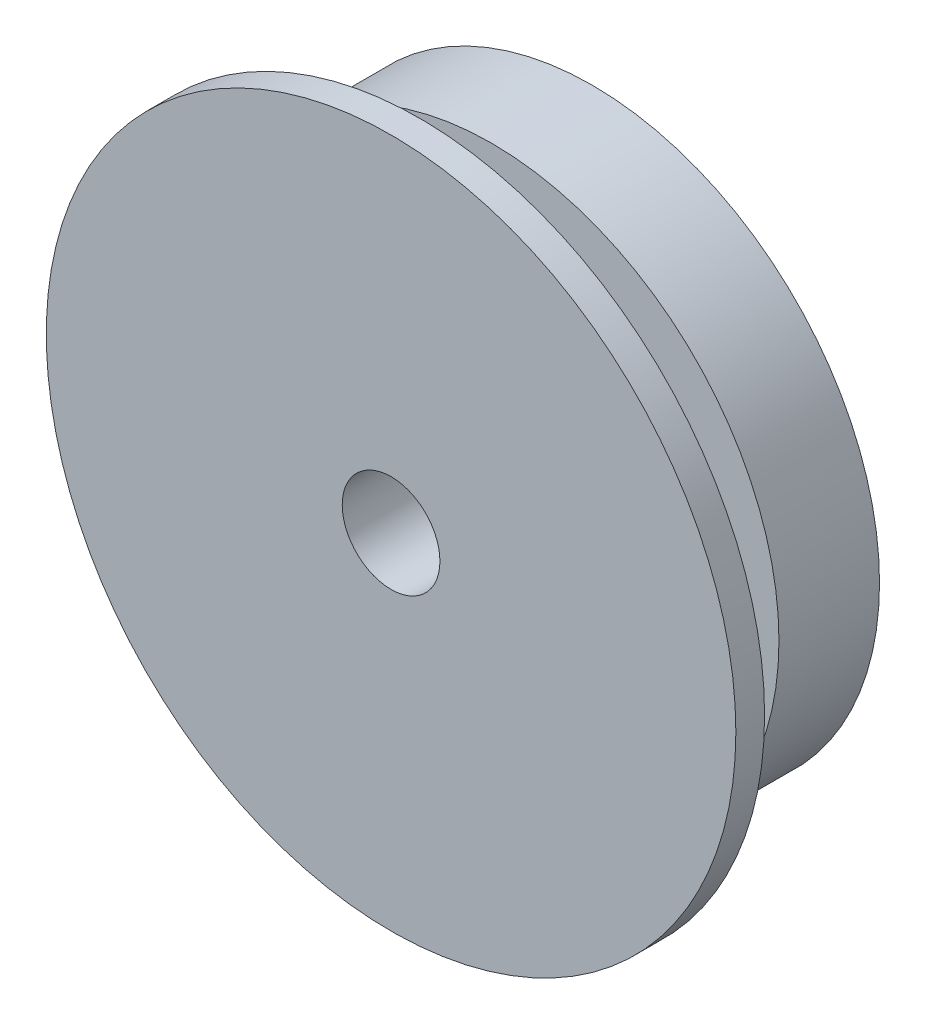
SolidWorks part; units mm, degrees
material "Resina de melamina"
ref_plane "Alzado" through (0, 0, 0) normal (0, 0, 1) x (1, 0, 0)
ref_plane "Planta" through (0, 0, 0) normal (0, 1, 0) x (1, 0, 0)
ref_plane "Vista lateral" through (0, 0, 0) normal (1, 0, 0) x (0, 0, -1)
sketch "Croquis1" plane through (0, 0, 0) normal (0, 0, 1) x (1, 0, 0)
  circle A0 centre (0, 0) radius 11
  circle A1 centre (0, 0) radius 25
  dimension "D1" = 50
  dimension "D2" = 22
extrude "Saliente-Extruir1" add sketch "Croquis1" along normal blind 19
ref_plane "Plano1" through (0, 0, 6) normal (0, 0, -1) x (-1, 0, 0)
sketch "Croquis3" plane through (0, 0, 6) normal (0, 0, -1) x (-1, 0, 0)
  circle A0 centre (0, 0) radius 11
  circle A1 centre (0, 0) radius 9.5
  dimension "D1" = 19
extrude "Saliente-Extruir2" add sketch "Croquis3" against normal through all
sketch "Croquis4" plane through (0, 0, 19) normal (0, 0, 1) x (1, 0, 0)
  circle A0 centre (0, 0) radius 11
  circle A1 centre (0, 0) radius 4
  dimension "D1" = 8
extrude "Saliente-Extruir3" add sketch "Croquis4" against normal blind 2
sketch "Croquis5" plane through (0, 0, 19) normal (0, 0, 1) x (1, 0, 0)
  circle A0 centre (0, 0) radius 25
  circle A1 centre (0, 0) radius 30
  dimension "D1" = 60
extrude "Saliente-Extruir4" add sketch "Croquis5" against normal blind 2.5
ref_plane "Plano2" through (0, 0, 14.25) normal (0, 0, -1) x (-1, 0, 0)
sketch "Croquis6" plane through (0, 0, 14.25) normal (0, 0, -1) x (-1, 0, 0)
  circle A1 centre (0, 0) radius 25
  circle A2 centre (0, 0) radius 19
  dimension "D1" = 38
extrude "Cortar-Extruir1" cut sketch "Croquis6" along normal blind 4
sketch "Croquis7" plane through (0, 0, 0) normal (0, 0, -1) x (-1, 0, 0)
  circle A0 centre (0, 0) radius 11
  circle A1 centre (0, 0) radius 4.25
  dimension "D1" = 8.5
extrude "Saliente-Extruir5" add sketch "Croquis7" against normal through all
sketch "Croquis8" plane through (0, 0, 0) normal (0, 0, -1) x (-1, 0, 0)
  circle A0 centre (0, 0) radius 4
  circle A1 centre (0, 0) radius 6.1
  dimension "D1" = 12.2
extrude "Saliente-Extruir6" add sketch "Croquis8" along normal blind 2
sketch "Croquis9" plane through (0, 0, 0) normal (0, 0, -1) x (-1, 0, 0)
  circle A0 centre (0, 0) radius 25
  circle A1 centre (0, 0) radius 15
  dimension "D1" = 30
extrude "Cortar-Extruir2" cut sketch "Croquis9" against normal blind 1.5
sketch "Croquis10" plane through (0, 0, 17) normal (0, 0, -1) x (-1, 0, 0)
  circle A0 centre (0, 0) radius 4.25
extrude "Cortar-Extruir3" cut sketch "Croquis10" against normal blind 10
sketch "Croquis11" plane through (0, 0, 0) normal (0, 0, 1) x (1, 0, 0)
  circle A0 centre (0, 0) radius 4.25
extrude "Cortar-Extruir4" cut sketch "Croquis11" against normal blind 10
